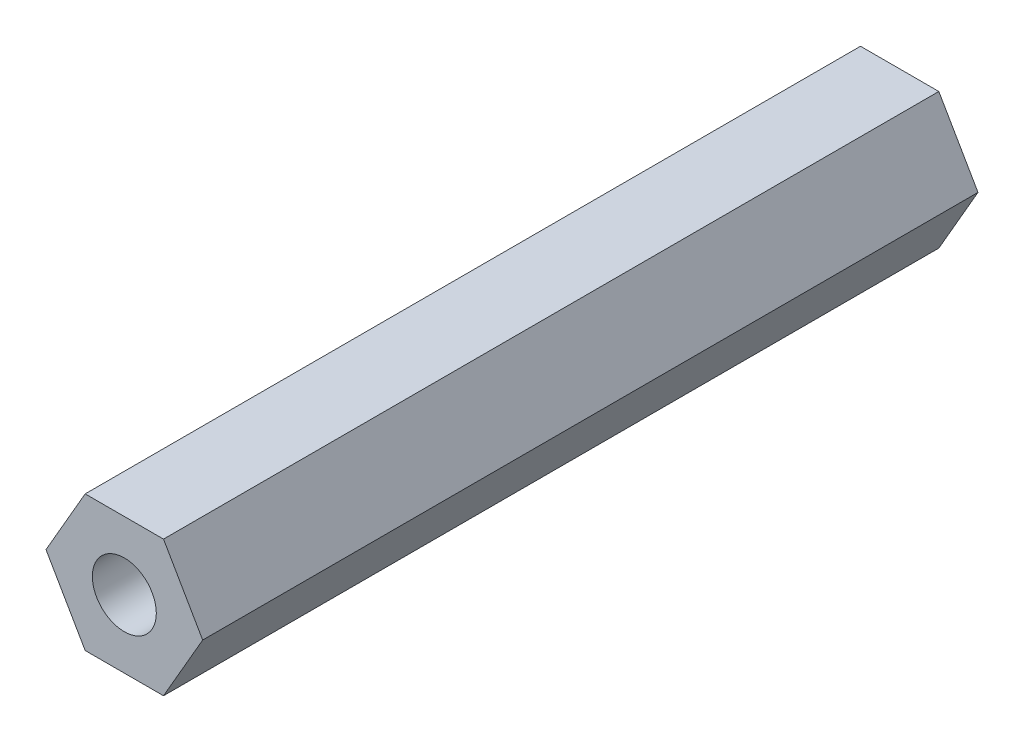
SolidWorks part; units mm, degrees
ref_plane "Front" through (0, 0, 0) normal (0, 0, 1) x (1, 0, 0)
ref_plane "Top" through (0, 0, 0) normal (0, 1, 0) x (1, 0, 0)
ref_plane "Right" through (0, 0, 0) normal (1, 0, 0) x (0, 0, -1)
sketch "Esquisse1" plane through (0, 0, 0) normal (0, 0, 1) x (1, 0, 0)
  line L1 (4.0415, 0) -> (2.0207, 3.5)
  line L2 (2.0207, 3.5) -> (-2.0207, 3.5)
  line L3 (-2.0207, 3.5) -> (-4.0415, 0)
  line L4 (-4.0415, 0) -> (-2.0207, -3.5)
  line L5 (-2.0207, -3.5) -> (2.0207, -3.5)
  line L6 (2.0207, -3.5) -> (4.0415, 0)
  circle A0 centre (0, 0) radius 3.5 construction
  dimension "D1" = 7
extrude "Boss.-Extru.1" add sketch "Esquisse1" along normal blind 40
sketch "Esquisse2" plane through (0, 0, 40) normal (0, 0, 1) x (1, 0, 0)
  circle A0 centre (0, 0) radius 1.65
  dimension "D1" = 3.3
extrude "Enlèv. mat.-Extru.1" cut sketch "Esquisse2" against normal blind 9
extrude "Enlèv. mat.-Extru.2" cut sketch "Esquisse2<2>" along normal blind 9 from vertex starting at point (2.0207, 3.5, 0)
sketch "Esquisse2<2>" plane through (0, 0, 40) normal (0, 0, 1) x (1, 0, 0) same geometry as "Esquisse2"
